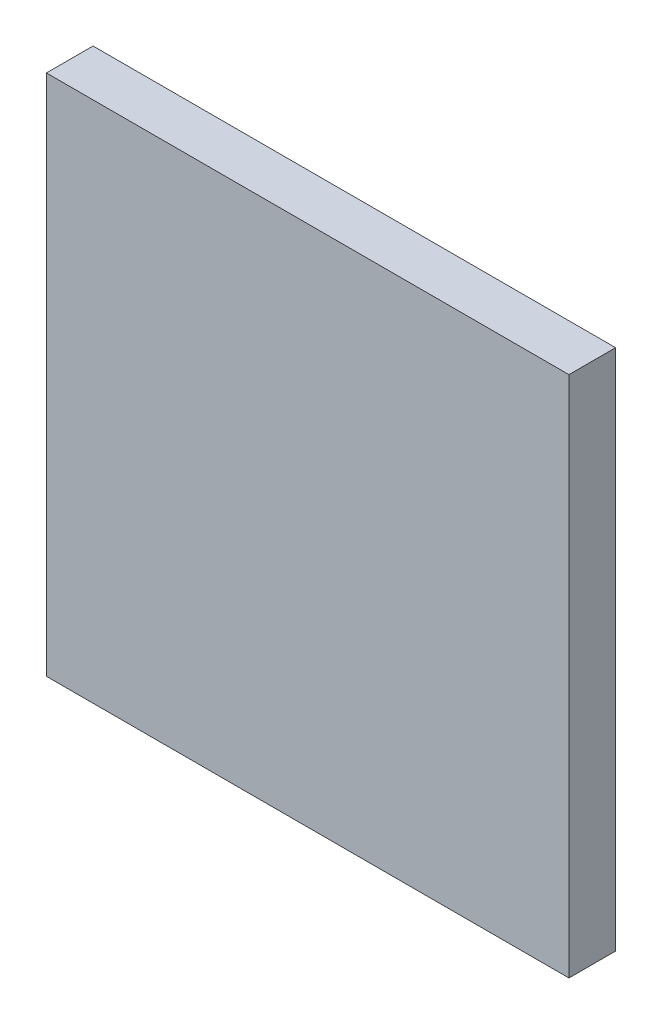
SolidWorks part; units mm, degrees
ref_plane "Front Plane" through (0, 0, 0) normal (0, 0, 1) x (1, 0, 0)
ref_plane "Top Plane" through (0, 0, 0) normal (0, 1, 0) x (1, 0, 0)
ref_plane "Right Plane" through (0, 0, 0) normal (1, 0, 0) x (0, 0, -1)
sketch "Sketch1" plane through (0, 0, 0) normal (0, 0, 1) x (1, 0, 0)
  line L4 (-28, 28) -> (-28, -28)
  line L5 (-28, -28) -> (28, -28)
  line L6 (28, -28) -> (28, 28)
  line L7 (28, 28) -> (-28, 28)
  line L8 (-28, 28) -> (-28, -28)
  line L9 (-28, -28) -> (28, -28)
  line L10 (28, -28) -> (28, 28)
  line L11 (28, 28) -> (-28, 28)
  line L16 (-26.5, -26.5) -> (26.5, -26.5)
  line L17 (26.5, -26.5) -> (26.5, 26.5)
  line L18 (26.5, 26.5) -> (-26.5, 26.5)
  line L19 (-26.5, 26.5) -> (-26.5, -26.5)
  line L20 (-26.5, -26.5) -> (26.5, -26.5)
  line L21 (26.5, -26.5) -> (26.5, 26.5)
  line L22 (26.5, 26.5) -> (-26.5, 26.5)
  line L23 (-26.5, 26.5) -> (-26.5, -26.5)
  line L28 (24.85, -24.85) -> (24.85, 24.85)
  line L29 (24.85, 24.85) -> (-24.85, 24.85)
  line L30 (-24.85, 24.85) -> (-24.85, -24.85)
  line L31 (-24.85, -24.85) -> (24.85, -24.85)
  line L32 (24.85, -24.85) -> (24.85, 24.85)
  line L33 (24.85, 24.85) -> (-24.85, 24.85)
  line L34 (-24.85, 24.85) -> (-24.85, -24.85)
  line L35 (-24.85, -24.85) -> (24.85, -24.85)
  dimension "D1" = 0
  dimension "D2" = 0.15
  dimension "D3" = 0.15
extrude "Boss-Extrude1" add sketch "Sketch1" along normal blind 2 contours L8 L9 L10 L11
extrude "Boss-Extrude2" add sketch "Sketch1<3>" against normal blind 3 contours L10 L11 L8 L9 L23 L22 L21 L20 region at (0, 27.208, 0)
sketch "Sketch1<3>" plane through (0, 0, 0) normal (0, 0, 1) x (1, 0, 0) same geometry as "Sketch1"
